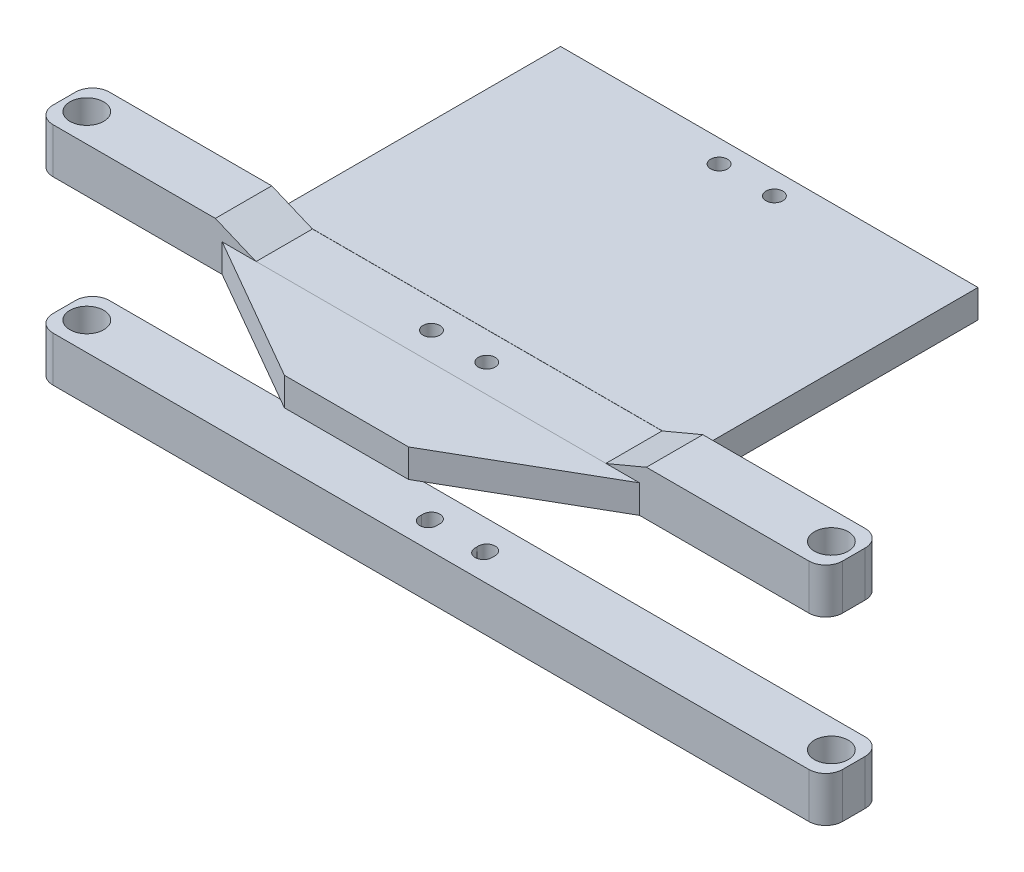
SolidWorks part; units mm, degrees
material "ABS"
ref_plane "Front Plane" through (0, 0, 0) normal (0, 0, 1) x (1, 0, 0)
ref_plane "Top Plane" through (0, 0, 0) normal (0, 1, 0) x (1, 0, 0)
ref_plane "Right Plane" through (0, 0, 0) normal (1, 0, 0) x (0, 0, -1)
sketch "Sketch1" plane through (0, 0, 0) normal (0, 1, 0) x (1, 0, 0)
  line L0 (-70, 10) -> (-15, 10)
  line L4 (15, 10) -> (70, 10)
  line L5 (70, 10) -> (70, 0)
  line L6 (-16.5, 0) -> (16.5, 0) construction
  line L7 (70, 0) -> (-70, 0)
  line L8 (-70, 0) -> (-70, 10)
  line L9 (0, -16.5) -> (0, 16.5) construction
  line L11 (-11, 10) -> (-15, 10)
  line L13 (11, 10) -> (15, 10)
  line L14 (-11, 10) -> (11, 10)
  circle A4 centre (-4.9, 5) radius 1.5
  circle A5 centre (4.9, 5) radius 1.5
  dimension "D12" = 4.9
  dimension "D10" = 3
  dimension "D11" = 9.8
  dimension "D2" = 5
  dimension "D4" = 55
  dimension "D5" = 55
  dimension "D7" = 10
  dimension "D8" = 4
  dimension "D9" = 4
extrude "Boss-Extrude1" add sketch "Sketch1" along normal blind 40 contours L11 | L13 | L14 L11 L0 L8 L7 L5 L4 L13 | L14 region at (0, 0, -5)
sketch "Sketch3" plane through (0, 0, 0) normal (1, 0, 0) x (0, 0, -1)
  line L0 (0, 16.5) -> (0, -16.5) construction
  line L1 (0, 8) -> (10, 8)
  line L2 (0, 8) -> (0, 32)
  line L3 (0, 32) -> (10, 32)
  line L4 (10, 8) -> (10, 32)
  line L6 (10, 40) -> (0, 40) construction
  line L7 (16.5, 0) -> (-16.5, 0) construction
  dimension "D1" = 8
  dimension "D2" = 8
  dimension "D3" = 10
extrude "Cut-Extrude1" cut sketch "Sketch3" against normal through all both and the other way through all
fillet "Fillet2" radius 3 4 edges at (70, 36, 0) (70, 36, -10) (-70, 36, -10) (-70, 36, 0)
fillet "Fillet3" radius 3 4 edges at (-70, 4, -10) (-70, 4, 0) (70, 4, 0) (70, 4, -10)
sketch "Sketch7" plane through (0, 0, 0) normal (0, 1, 0) x (1, 0, 0)
  line L0 (-37, 0) -> (37, 0)
  line L5 (-16.5, 0) -> (16.5, 0) construction
  line L6 (0, 0) -> (0, 10) construction
  line L11 (-10, 60) -> (10, 60)
  line L19 (-25, 0) -> (37, 0)
  line L20 (-37, 0) -> (-11, -14.9666)
  line L21 (-11, -14.9666) -> (11, -14.9666)
  line L22 (11, -14.9666) -> (37, 0)
  line L25 (-37, 0) -> (37, 0)
  line L26 (-37, 0) -> (-37, 60)
  line L27 (-37, 60) -> (37, 60)
  line L28 (37, 0) -> (37, 60)
  line L29 (-10, 60) -> (-10, 52.5)
  line L30 (-10, 52.5) -> (10, 52.5)
  line L31 (10, 60) -> (10, 52.5)
  line L32 (0, -16.5) -> (0, 16.5) construction
  circle A0 centre (-4.9, 56) radius 1.5
  circle A1 centre (4.9, 56) radius 1.5
  circle A2 centre (-4.9, 5) radius 1.5
  circle A3 centre (4.9, 5) radius 1.5
  dimension "D3" = 3
  dimension "D1" = 60
  dimension "D2" = 74
  dimension "D4" = 22
  dimension "D5" = 30
  dimension "D6" = 9.8
  dimension "D7" = 4.9
  dimension "D8" = 20
  dimension "D9" = 10
  dimension "D10" = 7.5
  dimension "D11" = 4
extrude "Boss-Extrude4" add sketch "Sketch7" along normal blind 5 from surface contours L21 L22 L0 L20 | L27 L31 L30 L29 L26 L0 L28 | L31 L11 L29 L30 A1 A0 region at (0, 0, -29.1618) region at (0, 0, 6.1322) region at (0, 0, -56.276) starting at face at (-4.9, 32, -3.5)
extrude "Boss-Extrude5" add sketch "Sketch7<5>" against normal blind 22 from surface contours L31 L11 L29 L30 A1 A0 region at (0, 0, -56.276) starting at face at (0, 32, -15.0111)
sketch "Sketch7<5>" plane through (0, 0, 0) normal (0, 1, 0) x (1, 0, 0) same geometry as "Sketch7"
sketch "Sketch5" plane through (0, 0, 0) normal (0, 1, 0) x (1, 0, 0)
  line L0 (0, -16.5) -> (0, 16.5) construction
  line L1 (-14, 1.4484) -> (14, 1.4484)
  line L2 (-14, 1.4484) -> (-14, 7.4484)
  line L3 (-14, 7.4484) -> (14, 7.4484)
  line L4 (14, 1.4484) -> (14, 7.4484)
  line L5 (-14, 1.4484) -> (14, 7.4484) construction
  line L6 (-14, 7.4484) -> (14, 1.4484) construction
  circle A0 centre (-4.9, 4.4484) radius 1.5
  circle A1 centre (4.9, 4.4484) radius 1.5
  point P0 (0, 4.4484)
  dimension "D3" = 3
  dimension "D1" = 28
  dimension "D2" = 6
  dimension "D4" = 9.8
  dimension "D5" = 4.9
extrude "Cut-Extrude4" cut sketch "Sketch5" against normal mid plane 22 contours A0 | A1 region at (-4.9, 0, -4.4484) region at (4.9, 0, -4.4484)
sketch "Sketch4" plane through (0, 0, 0) normal (0, 1, 0) x (1, 0, 0)
  line L0 (-16.5, 0) -> (16.5, 0) construction
  circle A0 centre (-66, 5) radius 3
  circle A1 centre (66, 5) radius 3
  dimension "D1" = 6
  dimension "D2" = 5
  dimension "D3" = 5
extrude "Cut-Extrude2" cut sketch "Sketch4" along normal through all both and the other way through all
sketch "Sketch9" plane through (0, 0, 0) normal (0, 0, 1) x (1, 0, 0)
  line L0 (-38.2109, 40) -> (-31, 36.9718)
  line L1 (67, 40) -> (-67, 40) construction
  line L2 (-31, 36.9718) -> (31, 36.9718)
  line L3 (31, 36.9718) -> (38.2109, 40)
  line L4 (38.2109, 40) -> (-38.2109, 40)
  line L5 (-37, 37) -> (-37, 32) construction
  line L6 (37, 37) -> (37, 32) construction
  dimension "D1" = 6
  dimension "D2" = 6
extrude "Cut-Extrude6" cut sketch "Sketch9" against normal blind 10
